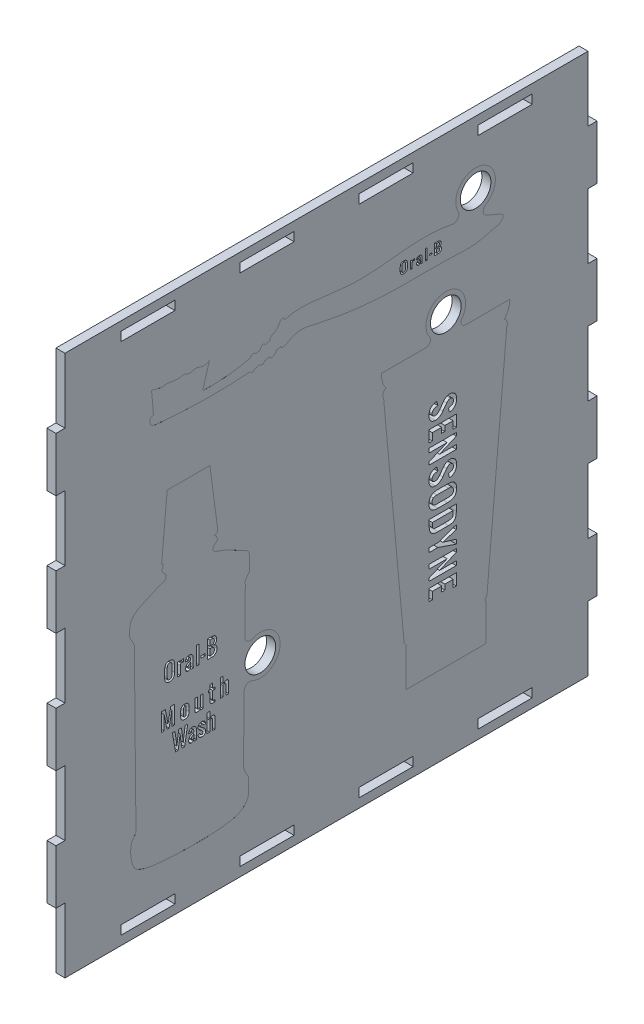
SolidWorks part; units mm, degrees
material "Maple"
ref_plane "Front Plane" through (0, 0, 0) normal (0, 0, 1) x (1, 0, 0)
ref_plane "Top Plane" through (0, 0, 0) normal (0, 1, 0) x (1, 0, 0)
ref_plane "Right Plane" through (0, 0, 0) normal (1, 0, 0) x (0, 0, -1)
sketch "Sketch1" plane through (0, 0, 0) normal (1, 0, 0) x (0, 0, -1)
  line L0 (-35.3846, 0) -> (34.2308, 0)
  line L1 (-145, -150) -> (145, -150)
  line L2 (-145, -150) -> (-145, 150) construction
  line L3 (-145, 150) -> (145, 150)
  line L4 (145, -150) -> (145, 150) construction
  line L5 (-145, -150) -> (145, 150) construction
  line L6 (-145, 150) -> (145, -150) construction
  line L7 (0, 33.2692) -> (0, -29.4231)
  line L8 (-150, 92.5) -> (-150, -92.5) construction
  line L9 (-145, 145) -> (145, 145) construction
  line L10 (-114, -140) -> (-84, -140)
  line L11 (-84, -145) -> (-84, -140)
  line L12 (-145, 150) -> (-145, 114)
  line L13 (-145, 114) -> (-150, 114)
  line L14 (-150, 114) -> (-150, 84)
  line L15 (-150, 84) -> (-145, 84)
  line L16 (150, 114) -> (150, 84)
  line L17 (150, 84) -> (145, 84)
  line L18 (145, 114) -> (150, 114)
  line L19 (145, 150) -> (145, 114)
  line L20 (-114, -145) -> (-84, -145)
  line L21 (-114, 145) -> (-84, 145)
  line L22 (-114, 145) -> (-114, 140)
  line L23 (-114, 140) -> (-84, 140)
  line L24 (-84, 145) -> (-84, 140)
  line L25 (-114, -145) -> (-114, -140)
  line L26 (-145, 84) -> (-145, 48)
  line L27 (-150, 48) -> (-150, 18)
  line L28 (-150, 18) -> (-145, 18)
  line L29 (145, 84) -> (145, 48)
  line L30 (145, 48) -> (150, 48)
  line L31 (150, 48) -> (150, 18)
  line L32 (150, 18) -> (145, 18)
  line L33 (-145, 48) -> (-150, 48)
  line L34 (-145, 18) -> (-145, -18)
  line L35 (-150, -18) -> (-150, -48)
  line L36 (-150, -48) -> (-145, -48)
  line L37 (145, 18) -> (145, -18)
  line L38 (145, -18) -> (150, -18)
  line L39 (150, -18) -> (150, -48)
  line L40 (150, -48) -> (145, -48)
  line L41 (-145, -18) -> (-150, -18)
  line L42 (-145, -48) -> (-145, -84)
  line L43 (-150, -84) -> (-150, -114)
  line L44 (-150, -114) -> (-145, -114)
  line L45 (145, -48) -> (145, -84)
  line L46 (145, -84) -> (150, -84)
  line L47 (150, -84) -> (150, -114)
  line L48 (150, -114) -> (145, -114)
  line L49 (-145, -84) -> (-150, -84)
  line L50 (-145, -114) -> (-145, -150)
  line L51 (145, -114) -> (145, -150)
  line L52 (-48, 145) -> (-48, 140)
  line L53 (-48, 145) -> (-18, 145)
  line L54 (-18, 145) -> (-18, 140)
  line L55 (-48, 140) -> (-18, 140)
  line L56 (-48, -140) -> (-18, -140)
  line L57 (-18, -145) -> (-18, -140)
  line L58 (-48, -145) -> (-18, -145)
  line L59 (-48, -145) -> (-48, -140)
  line L60 (18, 145) -> (18, 140)
  line L61 (18, 145) -> (48, 145)
  line L62 (48, 145) -> (48, 140)
  line L63 (18, 140) -> (48, 140)
  line L64 (18, -140) -> (48, -140)
  line L65 (48, -145) -> (48, -140)
  line L66 (18, -145) -> (48, -145)
  line L67 (18, -145) -> (18, -140)
  line L68 (84, 145) -> (84, 140)
  line L69 (84, 145) -> (114, 145)
  line L70 (114, 145) -> (114, 140)
  line L71 (84, 140) -> (114, 140)
  line L72 (84, -140) -> (114, -140)
  line L73 (114, -145) -> (114, -140)
  line L74 (84, -145) -> (114, -145)
  line L75 (84, -145) -> (84, -140)
  line L76 (-114, 142.5) -> (-150, 142.5)
  line L77 (-84, 142.5) -> (-48, 142.5)
  point P0 (0, 0)
  dimension "D1" = 30
  dimension "D2" = 5
  dimension "D4" = 300
  dimension "D5" = 300
  dimension "D7" = 5
  dimension "D3" = 4
  dimension "D6" = 4
extrude "Boss-Extrude1" add sketch "Sketch1" along normal mid plane 5 contours L21 L24 L52 L53 L54 L55 L23 L22 L12 L13 L14 L15 L26 L33 L27 L28 L34 L41 L35 L36 L42 L49 L43 L44 L50 L1 L51 L48 L47 L46 L45 L40 L39 L38 L37 L32 region at (0, -132, 140.7574)
sketch "Sketch2" plane through (2.5, 0, 0) normal (1, 0, 0) x (0, 0, -1)
  line L0 (-103.805, 83.6641) -> (84.0248, 85.8672) construction
  line L1 (-64.9288, 106.4569) -> (-68.6513, 93.7878)
  line L2 (-96.9816, 107.9556) -> (-95.8726, 95.5327)
  circle A0 centre (82.6585, 114.1691) radius 8.5
  circle A1 centre (82.6585, 114.1691) radius 11 construction
  arc A2 (72.9982, 108.9081) -> (69.8228, 104.5224) centre (70.3636, 107.4733) cw
  arc A3 (72.9982, 108.9081) -> (88.3141, 104.7343) centre (82.6585, 114.1691) cw
  arc A4 (88.3141, 104.7343) -> (88.7976, 99.3543) centre (89.8565, 102.1612) ccw
  spline S0 degree 3 poles (6.5525, 104.4755) (16.2684, 102.9345) (33.0134, 104.2463) (57.7385, 107.1926) (78.973, 102.9316) (90.9553, 98.7316) (98.7094, 95.0038) (96.4944, 91.4648) (91.7278, 90.9878) (83.0886, 87.9475) (64.662, 89.4058) (34.2571, 88.137) (5.7252, 91.4149) (-14.3848, 96.6768) (-20.3547, 94.2318) (-22.9189, 92.5456) (-25.3044, 92.1896) (-25.2927, 93.3515) knots 0 0 0 0 0.133177 0.227569 0.341196 0.412109 0.424808 0.435895 0.455974 0.488682 0.560107 0.702904 0.90474 0.954569 0.976853 0.98794 1 1 1 1
  spline S1 degree 1 poles (-25.2927, 93.3515) (-28.0596, 92.6972) knots 0 0 1 1
  spline S2 degree 3 poles (-28.0596, 92.6972) (-27.8287, 90.8983) (-31.6114, 89.672) (-31.7862, 91.8044) knots 0 0 0 0 1 1 1 1
  spline S3 degree 1 poles (-31.7862, 91.8044) (-34.374, 90.9522) knots 0 0 1 1
  spline S4 degree 2 poles (-34.374, 90.9522) (-35.327, 88.9008) (-37.169, 90.4587) knots 0 0 0 1 1 1
  spline S5 degree 1 poles (-37.169, 90.4587) (-39.7568, 89.818) knots 0 0 1 1
  spline S6 degree 2 poles (-39.7568, 89.818) (-41.1273, 88.159) (-42.5517, 89.818) knots 0 0 0 1 1 1
  spline S7 degree 3 poles (-42.5517, 89.818) (-55.7829, 88.5362) (-74.5574, 88.9284) (-91.126, 90.1625) (-97.6029, 90.8687) (-97.837, 93.4725) (-97.9211, 96.0213) (-96.2777, 95.4349) (-95.8726, 95.5327) knots 0 0 0 0 0.683272 0.847161 0.913324 0.939394 0.976423 1 1 1 1
  spline S8 degree 3 poles (-96.9816, 107.9556) (-95.1572, 108.0377) (-92.2331, 106.176) (-88.4707, 107.3482) (-85.9029, 106.6264) (-83.8994, 106.6299) (-81.5057, 106.1616) (-79.0534, 107.2928) (-76.9027, 105.7554) (-74.5329, 105.9127) (-72.0913, 106.8487) (-68.9379, 105.1119) (-66.2637, 105.4954) (-64.9288, 106.4569) knots 0 0 0 0 0.164786 0.287539 0.337088 0.406149 0.470446 0.558401 0.626387 0.691386 0.769448 0.854065 1 1 1 1
  spline S9 degree 2 poles (-68.6513, 93.7878) (-55.1915, 93.1744) (-42.0352, 96.4052) knots 0 0 0 1 1 1
  spline S10 degree 3 poles (-42.0352, 96.4052) (-41.9645, 97.6813) (-39.791, 98.0736) (-39.4213, 96.8815) knots 0 0 0 0 1 1 1 1
  spline S11 degree 1 poles (-36.6699, 97.363) (-39.4213, 96.8815) knots 0 0 1 1
  spline S12 degree 3 poles (-36.6699, 97.363) (-36.6714, 98.6626) (-34.5693, 100.4662) (-33.8498, 98.4635) knots 0 0 0 0 1 1 1 1
  spline S13 degree 1 poles (-33.8498, 98.4635) (-31.3721, 99.3578) knots 0 0 1 1
  spline S14 degree 3 poles (-31.3721, 99.3578) (-31.5133, 100.8043) (-29.3265, 101.6154) (-26.3053, 103.4262) (-25.9522, 106.0297) (-24.495, 106.4569) knots 0 0 0 0 0.331857 0.63536 1 1 1 1
  spline S15 degree 2 poles (-24.495, 106.4569) (-23.3753, 106.347) (-23.1115, 105.1401) knots 0 0 0 1 1 1
  spline S16 degree 3 poles (6.5525, 104.4755) (-3.0815, 105.0737) (-13.4853, 108.1798) (-23.1115, 105.1401) knots 0 0 0 0 1 1 1 1
  point P81 (0, 0)
  point P82 (0, 0)
  point P83 (84.1802, 119.7003)
  point P84 (84.1802, 119.7003)
  point P85 (0, 0)
extrude "Cut-Extrude1" cut sketch "Sketch2" against normal through all contours S0 S16 S15 S14 S13 S12 S11 S10 S9 L1 S8 L2 S7 S6 S5 S4 S3 S2 S1 | A2 S0 A4 A3 A0 | A0 region at (2.5, 97.1703, -2.8666) region at (2.5, 105.5078, -73.0782) region at (2.5, 114.1691, -82.6585)
sketch "Sketch3" plane through (2.5, 0, 0) normal (1, 0, 0) x (0, 0, -1)
  line L0 (-25.3812, -30.9825) -> (162.6317, -33) construction
  line L1 (31.6753, 39.8057) -> (43.0136, -82.9441)
  line L2 (44.0297, -85.902) -> (44.0297, -106.1138)
  line L3 (44.0297, -106.1138) -> (88.3586, -106.1138)
  line L4 (88.3586, -106.1138) -> (88.3586, -85.902)
  line L5 (88.9681, -82.9441) -> (99.9172, 39.8057)
  line L6 (101.6714, 52.5676) -> (30.6093, 52.5676)
  circle A0 centre (66.1403, 62.9692) radius 8.5
  circle A1 centre (66.1403, 62.9692) radius 11 construction
  arc A2 (57.2067, 56.5513) -> (55.1635, 52.5676) centre (55.1635, 55.0834) cw
  arc A3 (57.2067, 56.5513) -> (75.074, 56.5513) centre (66.1403, 62.9692) cw
  arc A4 (75.074, 56.5513) -> (77.1172, 52.5676) centre (77.1172, 55.0834) ccw
  spline S0 degree 2 poles (30.6093, 52.5676) (30.0746, 47.7888) (33.0459, 44.4632) knots 0 0 0 1 1 1
  spline S1 degree 2 poles (33.0459, 44.4632) (30.5043, 42.9078) (31.6753, 39.8057) knots 0 0 0 1 1 1
  spline S2 degree 2 poles (101.6714, 52.5676) (101.4143, 47.9068) (98.5767, 44.4632) knots 0 0 0 1 1 1
  spline S3 degree 2 poles (98.5767, 44.4632) (101.0752, 42.8843) (99.9172, 39.8057) knots 0 0 0 1 1 1
  spline S4 degree 2 poles (43.0136, -82.9441) (43.193, -84.2249) (44.4027, -84.7365) knots 0 0 0 1 1 1
  spline S5 degree 2 poles (44.4027, -84.7365) (43.7281, -85.1056) (44.0297, -85.902) knots 0 0 0 1 1 1
  spline S6 degree 2 poles (88.9681, -82.9441) (88.6722, -84.1285) (87.6529, -84.7365) knots 0 0 0 1 1 1
  spline S7 degree 2 poles (87.6529, -84.7365) (88.2852, -85.1047) (88.3586, -85.902) knots 0 0 0 1 1 1
  point P33 (0, 0)
  point P34 (66.1403, 52.5676)
  point P35 (0, 0)
  point P36 (0, 0)
  point P37 (0, 0)
  point P38 (0, 0)
  point P39 (0, 0)
  point P40 (80.7843, 50.0055)
  point P41 (81.0172, 51.8688)
  point P42 (66.1403, 62.9692)
  point P43 (55.1635, 52.5676)
  dimension "D1" = 11
  dimension "D2" = 17
extrude "Cut-Extrude4" cut sketch "Sketch3" against normal through all contours L1 L0 L5 S3 S2 L6 S0 S1 | A4 A3 A2 L6 A0 | A0 | S7 L4 L3 L2 S5 S4 L1 S1 S0 L6 S2 S3 L5 S6 region at (2.5, -20.1434, -65.9177) region at (2.5, 53.7952, -57.6751) region at (2.5, 62.9692, -66.1403)
sketch "Sketch4" plane through (2.5, 0, 0) normal (1, 0, 0) x (0, 0, -1)
  line L0 (56.9565, 29.9553) -> (56.9565, -75.6719) construction
  text T0 "SENSODYNE" font "Oswald" height 15
sketch "Sketch5" plane through (2.5, 0, 0) normal (1, 0, 0) x (0, 0, -1)
  line L0 (-164.1642, 33.9777) -> (0, 33.9777) construction
  line L1 (-64.6546, 55.9013) -> (-88.3352, 55.9013)
  line L2 (-88.3352, 55.9013) -> (-91.3122, 23.0192)
  line L3 (-64.6546, 55.9013) -> (-60.3245, 23.0192)
  line L4 (-106.526, -10.8034) -> (-105.639, -99.3563)
  line L5 (-45.0182, -10.8034) -> (-46.061, -98.1311)
  line L6 (-43.2783, -104.3785) -> (-43.2783, -112.242)
  circle A0 centre (-36.6998, -49.1357) radius 8.5
  circle A1 centre (-36.6998, -49.1357) radius 11 construction
  arc A2 (-41.1177, -39.0618) -> (-45.3224, -36.2786) centre (-42.3226, -36.3144) cw
  arc A3 (-41.1177, -39.0618) -> (-41.357, -59.1011) centre (-36.6998, -49.1357) cw
  arc A4 (-41.357, -59.1011) -> (-45.627, -61.7832) centre (-42.6272, -61.819) ccw
  spline S0 degree 3 poles (-46.061, -98.1311) (-45.5535, -100.3758) (-44.3748, -102.3812) (-43.2783, -104.3785) knots 0 0 0 0 1 1 1 1
  spline S1 degree 3 poles (-43.2783, -112.242) (-43.4166, -115.0045) (-46.5872, -118.7905) (-53.4587, -120.7059) (-62.491, -121.5767) (-74.8863, -121.9531) (-89.4824, -121.1309) (-100.1013, -120.2727) (-106.6348, -117.0775) (-108.4782, -111.9364) (-108.7832, -106.9022) (-107.8798, -102.1735) (-105.9409, -100.7903) (-105.639, -99.3563) knots 0 0 0 0 0.091092 0.156397 0.243947 0.407749 0.586765 0.756523 0.770177 0.837032 0.92551 0.950709 1 1 1 1
  spline S2 degree 2 poles (-91.3122, 23.0192) (-91.6801, 21.7652) (-90.3186, 21.1745) knots 0 0 0 1 1 1
  spline S3 degree 2 poles (-60.3245, 23.0192) (-60.2552, 21.1929) (-62.4896, 21.1745) knots 0 0 0 1 1 1
  spline S4 degree 3 poles (-62.4896, 21.1745) (-61.2991, 20.9908) (-59.3865, 17.7511) (-62.4979, 16.7748) (-63.1688, 15.0158) (-62.2048, 13.0592) (-58.0441, 12.0721) (-52.9127, 9.4872) (-47.7641, 6.5137) (-43.2354, 4.6448) (-42.275, 0.4691) (-42.9963, -2.6108) (-42.4325, -6.0325) (-44.4143, -7.916) (-45.4392, -9.558) (-45.0182, -10.8034) knots 0 0 0 0 0.086801 0.139575 0.170697 0.196999 0.27023 0.427059 0.575154 0.667009 0.715592 0.836361 0.876038 0.926558 1 1 1 1
  spline S5 degree 3 poles (-90.3186, 21.1745) (-91.011, 20.2151) (-91.7958, 17.3683) (-88.9651, 16.3382) (-88.9562, 14.8445) (-89.0422, 13.033) (-92.603, 12.2808) (-96.8466, 10.2172) (-102.747, 7.9178) (-108.5698, 4.3722) (-109.1107, -0.4843) (-109.8272, -5.3852) (-106.2449, -8.1823) (-106.526, -10.8034) knots 0 0 0 0 0.086306 0.139113 0.156983 0.18213 0.252943 0.352661 0.518218 0.680568 0.758803 0.835283 1 1 1 1
  point P59 (0, 0)
  dimension "D1" = 11
extrude "Cut-Extrude7" cut sketch "Sketch5" against normal through all contours S2 S5 L4 S1 L6 S0 L5 S4 S3 L3 L1 L2 | A4 A3 A2 L5 A0 | A0 region at (2.5, -43.2536, 75.8314) region at (2.5, -39.0859, 44.1572) region at (2.5, -49.1357, 36.6998)
sketch "Sketch6" plane through (2.5, 0, 0) normal (1, 0, 0) x (0, 0, -1)
  line L0 (-90.2637, -36.7166) -> (-62.9603, -36.7166) construction
  line L1 (-92.3146, -58.8925) -> (-54.5001, -58.8925) construction
  line L2 (-92.3146, -72.0955) -> (-54.5001, -72.0955) construction
  text T0 "Oral-B" font "Oswald" height 10
  text T1 "Mouth" font "Oswald" height 10
  text T2 "Wash" font "Oswald" height 10
  point P7 (-73.4074, -58.8925)
  point P8 (-73.4074, -72.0955)
sketch "Sketch7" plane through (2.5, 0, 0) normal (1, 0, 0) x (0, 0, -1)
  line L0 (31.3279, 94.3287) -> (73.1618, 94.3287) construction
  text T0 "Oral-B" font "Oswald" height 6
sketch "Sketch8" plane through (2.5, 0, 0) normal (1, 0, 0) x (0, 0, -1)
  line L0 (-43.2783, -112.242) -> (-43.2783, -104.3785) construction
  line L1 (-64.6546, 55.9013) -> (-88.3352, 55.9013) construction
  line L3 (-106.526, -10.8034) -> (-105.639, -99.3563) construction
  line L4 (-60.3245, 23.0192) -> (-64.6546, 55.9013) construction
  line L5 (-88.3352, 55.9013) -> (-91.3122, 23.0192) construction
  line L6 (-43.2783, -112.242) -> (-43.2783, -104.3785)
  line L7 (-64.6546, 55.9013) -> (-88.3352, 55.9013)
  line L9 (-106.526, -10.8034) -> (-105.639, -99.3563)
  line L10 (-60.3245, 23.0192) -> (-64.6546, 55.9013)
  line L11 (-88.3352, 55.9013) -> (-91.3122, 23.0192)
  line L12 (101.6714, 52.5676) -> (77.1172, 52.5676) construction
  line L13 (88.3586, -106.1138) -> (88.3586, -85.902) construction
  line L14 (44.0297, -85.902) -> (44.0297, -106.1138) construction
  line L15 (44.0297, -106.1138) -> (88.3586, -106.1138) construction
  line L16 (88.9681, -82.9441) -> (99.9172, 39.8057) construction
  line L18 (31.6753, 39.8057) -> (43.0136, -82.9441) construction
  line L19 (88.3586, -106.1138) -> (88.3586, -85.902)
  line L20 (44.0297, -85.902) -> (44.0297, -106.1138)
  line L21 (44.0297, -106.1138) -> (88.3586, -106.1138)
  line L22 (88.9681, -82.9441) -> (99.9172, 39.8057)
  line L24 (31.6753, 39.8057) -> (43.0136, -82.9441)
  line L30 (-68.6513, 93.7878) -> (-64.9288, 106.4569) construction
  line L31 (-96.9816, 107.9556) -> (-95.8726, 95.5327) construction
  line L32 (-33.8498, 98.4635) -> (-31.3721, 99.3578)
  line L33 (-39.4213, 96.8815) -> (-36.6699, 97.363)
  line L34 (-37.169, 90.4587) -> (-39.7568, 89.818)
  line L35 (-31.7862, 91.8044) -> (-34.374, 90.9522)
  line L36 (-25.2927, 93.3515) -> (-28.0596, 92.6972)
  line L37 (-68.6513, 93.7878) -> (-64.9288, 106.4569)
  line L38 (-96.9816, 107.9556) -> (-95.8726, 95.5327)
  line L39 (55.1635, 52.5676) -> (30.6093, 52.5676) construction
  line L40 (101.6714, 52.5676) -> (77.1172, 52.5676)
  line L41 (55.1635, 52.5676) -> (30.6093, 52.5676)
  line L42 (-45.0182, -10.8034) -> (-45.3224, -36.2786) construction
  line L43 (-45.627, -61.7832) -> (-46.061, -98.1311) construction
  line L44 (-45.0182, -10.8034) -> (-45.3224, -36.2786)
  line L45 (-45.627, -61.7832) -> (-46.061, -98.1311)
  arc A1 (88.3141, 104.7343) -> (88.7976, 99.3543) centre (89.8565, 102.1612) ccw construction
  arc A2 (88.3141, 104.7343) -> (72.9982, 108.9081) centre (82.6585, 114.1691) ccw construction
  arc A3 (69.8228, 104.5224) -> (72.9982, 108.9081) centre (70.3636, 107.4733) ccw construction
  circle A4 centre (82.6585, 114.1691) radius 8.5
  arc A5 (88.3141, 104.7343) -> (88.7976, 99.3543) centre (89.8565, 102.1612) ccw
  arc A6 (88.3141, 104.7343) -> (72.9982, 108.9081) centre (82.6585, 114.1691) ccw
  arc A7 (69.8228, 104.5224) -> (72.9982, 108.9081) centre (70.3636, 107.4733) ccw
  arc A8 (75.074, 56.5513) -> (77.1172, 52.5676) centre (77.1172, 55.0834) ccw construction
  arc A10 (55.1635, 52.5676) -> (57.2067, 56.5513) centre (55.1635, 55.0834) ccw construction
  arc A12 (75.074, 56.5513) -> (77.1172, 52.5676) centre (77.1172, 55.0834) ccw
  circle A13 centre (66.1403, 62.9692) radius 8.5
  arc A14 (55.1635, 52.5676) -> (57.2067, 56.5513) centre (55.1635, 55.0834) ccw
  arc A15 (75.074, 56.5513) -> (57.2067, 56.5513) centre (66.1403, 62.9692) ccw
  arc A16 (-41.357, -59.1011) -> (-45.627, -61.7832) centre (-42.6272, -61.819) ccw construction
  arc A18 (-41.357, -59.1011) -> (-41.1177, -39.0618) centre (-36.6998, -49.1357) ccw construction
  arc A19 (-45.3224, -36.2786) -> (-41.1177, -39.0618) centre (-42.3226, -36.3144) ccw construction
  arc A20 (-41.357, -59.1011) -> (-45.627, -61.7832) centre (-42.6272, -61.819) ccw
  circle A21 centre (-36.6998, -49.1357) radius 8.5
  arc A22 (-41.357, -59.1011) -> (-41.1177, -39.0618) centre (-36.6998, -49.1357) ccw
  arc A23 (-45.3224, -36.2786) -> (-41.1177, -39.0618) centre (-42.3226, -36.3144) ccw
  parabola Q0 (-62.4896, 21.1745) -> (-60.3245, 23.0192) focus (-61.1658, 22.2491) apex (-60.6439, 21.8394) construction
  parabola Q1 (-91.3122, 23.0192) -> (-90.3186, 21.1745) focus (-90.7661, 22.2763) apex (-91.3104, 22.0676) construction
  parabola Q2 (-62.4896, 21.1745) -> (-60.3245, 23.0192) focus (-61.1658, 22.2491) apex (-60.6439, 21.8394)
  parabola Q3 (-91.3122, 23.0192) -> (-90.3186, 21.1745) focus (-90.7661, 22.2763) apex (-91.3104, 22.0676)
  parabola Q4 (87.6529, -84.7365) -> (88.3586, -85.902) focus (87.5479, -85.4891) apex (88.0641, -85.0928) construction
  parabola Q5 (88.9681, -82.9441) -> (87.6529, -84.7365) focus (87.3836, -83.2377) apex (88.4267, -84.069) construction
  parabola Q6 (44.4027, -84.7365) -> (44.0297, -85.902) focus (44.3159, -85.2845) apex (43.9975, -85.1451) construction
  parabola Q7 (43.0136, -82.9441) -> (44.4027, -84.7365) focus (44.2296, -83.4059) apex (43.4286, -84.0038) construction
  parabola Q8 (87.6529, -84.7365) -> (88.3586, -85.902) focus (87.5479, -85.4891) apex (88.0641, -85.0928)
  parabola Q9 (88.9681, -82.9441) -> (87.6529, -84.7365) focus (87.3836, -83.2377) apex (88.4267, -84.069)
  parabola Q10 (44.4027, -84.7365) -> (44.0297, -85.902) focus (44.3159, -85.2845) apex (43.9975, -85.1451)
  parabola Q11 (43.0136, -82.9441) -> (44.4027, -84.7365) focus (44.2296, -83.4059) apex (43.4286, -84.0038)
  parabola Q12 (33.0459, 44.4632) -> (31.6753, 39.8057) focus (32.8746, 42.2623) apex (31.538, 42.8192) construction
  parabola Q14 (98.5767, 44.4632) -> (99.9172, 39.8057) focus (98.6969, 42.2561) apex (100.0554, 42.8133) construction
  parabola Q15 (101.6714, 52.5676) -> (98.5767, 44.4632) focus (94.448, 50.0889) apex (100.3776, 47.2918) construction
  parabola Q16 (33.0459, 44.4632) -> (31.6753, 39.8057) focus (32.8746, 42.2623) apex (31.538, 42.8192)
  parabola Q18 (98.5767, 44.4632) -> (99.9172, 39.8057) focus (98.6969, 42.2561) apex (100.0554, 42.8133)
  parabola Q19 (101.6714, 52.5676) -> (98.5767, 44.4632) focus (94.448, 50.0889) apex (100.3776, 47.2918)
  parabola Q22 (-23.1115, 105.1401) -> (-24.495, 106.4569) focus (-24.0856, 105.6445) apex (-23.6862, 106.1563) construction
  parabola Q23 (-42.0352, 96.4052) -> (-68.6513, 93.7878) focus (-60.6914, 140.1901) apex (-57.0417, 93.9781) construction
  parabola Q24 (-42.5517, 89.818) -> (-39.7568, 89.818) focus (-41.1312, 89.577) apex (-41.1217, 88.9887)
  parabola Q25 (-37.169, 90.4587) -> (-34.374, 90.9522) focus (-35.6076, 90.3417) apex (-35.4786, 89.818)
  parabola Q26 (-23.1115, 105.1401) -> (-24.495, 106.4569) focus (-24.0856, 105.6445) apex (-23.6862, 106.1563)
  parabola Q27 (-42.0352, 96.4052) -> (-68.6513, 93.7878) focus (-60.6914, 140.1901) apex (-57.0417, 93.9781)
  parabola Q28 (30.6093, 52.5676) -> (33.0459, 44.4632) focus (35.5827, 49.0483) apex (31.269, 47.2602)
  spline S0 degree 3 poles (-2742.5498, 1330.6542) (5.6091, -122.6957) (-104.8352, -86.237) (-108.7832, -106.9022) (-108.4782, -111.9364) (-106.6348, -117.0775) (-100.1013, -120.2727) (-89.4824, -121.1309) (-74.8863, -121.9531) (-62.491, -121.5767) (-53.4587, -120.7059) (-15.6966, -110.1803) (-59.6585, 63.8728) (-3031.5563, -311.9062) knots -0.549236 -0.549236 -0.549236 -0.549236 0.049291 0.07449 0.162968 0.229823 0.243477 0.413235 0.592251 0.756053 0.843603 0.908908 2.096664 2.096664 2.096664 2.096664 only from (-105.639, -99.3563) to (-43.2783, -112.242) construction
  spline S1 degree 3 poles (-2885.8008, -1060.6798) (2862.4928, 742.5463) (-2944.3638, -964.9011) (2782.6842, 897.2561) knots -15.55403 -15.55403 -15.55403 -15.55403 15.743313 15.743313 15.743313 15.743313 only from (-43.2783, -104.3785) to (-46.061, -98.1311) construction
  spline S2 degree 3 poles (-1575.2983, -2584.2378) (85.9785, 158.0196) (-109.5975, 23.8459) (-88.9651, 16.3382) (-88.9562, 14.8445) (-89.0422, 13.033) (-92.603, 12.2808) (-96.8466, 10.2172) (-102.747, 7.9178) (-108.5698, 4.3722) (-109.1107, -0.4843) (-112.7776, -25.5685) (55.4837, -11.8156) (-3004.0815, -786.4549) knots -0.987214 -0.987214 -0.987214 -0.987214 0.086306 0.139113 0.156983 0.18213 0.252943 0.352661 0.518218 0.680568 0.758803 0.835283 2.315501 2.315501 2.315501 2.315501 only from (-90.3186, 21.1745) to (-106.526, -10.8034) construction
  spline S4 degree 3 poles (-43.2783, -104.3785) (-44.3748, -102.3812) (-45.5535, -100.3758) (-46.061, -98.1311) knots 0 0 0 0 1 1 1 1
  spline S5 degree 3 poles (-105.639, -99.3563) (-105.9409, -100.7903) (-107.8798, -102.1735) (-108.7832, -106.9022) (-108.4782, -111.9364) (-106.6348, -117.0775) (-100.1013, -120.2727) (-89.4824, -121.1309) (-74.8863, -121.9531) (-62.491, -121.5767) (-53.4587, -120.7059) (-46.5872, -118.7905) (-43.4166, -115.0045) (-43.2783, -112.242) knots 0 0 0 0 0.049291 0.07449 0.162968 0.229823 0.243477 0.413235 0.592251 0.756053 0.843603 0.908908 1 1 1 1
  spline S6 degree 3 poles (-90.3186, 21.1745) (-91.011, 20.2151) (-91.7958, 17.3683) (-88.9651, 16.3382) (-88.9562, 14.8445) (-89.0422, 13.033) (-92.603, 12.2808) (-96.8466, 10.2172) (-102.747, 7.9178) (-108.5698, 4.3722) (-109.1107, -0.4843) (-109.8272, -5.3852) (-106.2449, -8.1823) (-106.526, -10.8034) knots 0 0 0 0 0.086306 0.139113 0.156983 0.18213 0.252943 0.352661 0.518218 0.680568 0.758803 0.835283 1 1 1 1
  spline S7 degree 3 poles (-45.0182, -10.8034) (-45.4392, -9.558) (-44.4143, -7.916) (-42.4325, -6.0325) (-42.9963, -2.6108) (-42.275, 0.4691) (-43.2354, 4.6448) (-47.7641, 6.5137) (-52.9127, 9.4872) (-58.0441, 12.0721) (-62.2048, 13.0592) (-63.1688, 15.0158) (-62.4979, 16.7748) (-59.3865, 17.7511) (-61.2991, 20.9908) (-62.4896, 21.1745) knots 0 0 0 0 0.073442 0.123962 0.163639 0.284408 0.332991 0.424846 0.572941 0.72977 0.803001 0.829303 0.860425 0.913199 1 1 1 1
  spline S14 degree 3 poles (-1831.8486, 2540.3951) (-20.7773, 9.9839) (-98.2602, 106.2938) (-97.837, 93.4725) (-97.6029, 90.8687) (-91.126, 90.1625) (32.9365, 80.9219) (373.4952, 119.8653) (-2821.2546, 1206.7555) knots -0.349331 -0.349331 -0.349331 -0.349331 0.023577 0.060606 0.086676 0.152839 0.316728 6.925471 6.925471 6.925471 6.925471 only from (-95.8726, 95.5327) to (-42.5517, 89.818) construction
  spline S15 degree 3 poles (-2902.3044, 1054.9753) (31.6857, 319.1533) (-42.9103, 90.7771) (-72.0913, 106.8487) (-74.5329, 105.9127) (-76.9027, 105.7554) (-79.0534, 107.2928) (-81.5057, 106.1616) (-83.8994, 106.6299) (-85.9029, 106.6264) (-88.4707, 107.3482) (-111.9493, 100.0337) (-120.3168, 238.9042) (-505.4382, -2863.6554) knots -2.547225 -2.547225 -2.547225 -2.547225 0.145935 0.230552 0.308614 0.373613 0.441599 0.529554 0.593851 0.662912 0.712461 0.835214 2.76644 2.76644 2.76644 2.76644 only from (-64.9288, 106.4569) to (-96.9816, 107.9556) construction
  spline S16 degree 3 poles (-33.8498, 98.4635) (-34.5693, 100.4662) (-36.6714, 98.6626) (-36.6699, 97.363) knots 0 0 0 0 1 1 1 1
  spline S17 degree 3 poles (-39.4213, 96.8815) (-39.791, 98.0736) (-41.9645, 97.6813) (-42.0352, 96.4052) knots 0 0 0 0 1 1 1 1
  spline S18 degree 3 poles (-31.7862, 91.8044) (-31.6114, 89.672) (-27.8287, 90.8983) (-28.0596, 92.6972) knots 0 0 0 0 1 1 1 1
  spline S19 degree 3 poles (-24.495, 106.4569) (-25.9522, 106.0297) (-26.3053, 103.4262) (-29.3265, 101.6154) (-31.5133, 100.8043) (-31.3721, 99.3578) knots 0 0 0 0 0.36464 0.668143 1 1 1 1
  spline S20 degree 3 poles (6.5525, 104.4755) (-3.0815, 105.0737) (-13.4853, 108.1798) (-23.1115, 105.1401) knots 0 0 0 0 1 1 1 1
  spline S21 degree 3 poles (-2620.0063, 1387.0751) (149.1048, -2.32) (25.8344, 130.0388) (98.7094, 95.0038) (96.4944, 91.4648) (91.7278, 90.9878) (83.0886, 87.9475) (64.662, 89.4058) (34.2571, 88.137) (5.7252, 91.4149) (-14.3848, 96.6768) (-20.3547, 94.2318) (-30.1514, 87.7896) (-84.7849, 103.6645) (2256.2114, 2039.2052) knots -0.45411 -0.45411 -0.45411 -0.45411 0.412109 0.424808 0.435895 0.455974 0.488682 0.560107 0.702904 0.90474 0.954569 0.976853 0.98794 1.128142 1.128142 1.128142 1.128142 only from (88.7976, 99.3543) to (-25.2927, 93.3515) construction
  spline S22 degree 3 poles (-95.8726, 95.5327) (-96.2777, 95.4349) (-97.9211, 96.0213) (-97.837, 93.4725) (-97.6029, 90.8687) (-91.126, 90.1625) (-74.5574, 88.9284) (-55.7829, 88.5362) (-42.5517, 89.818) knots 0 0 0 0 0.023577 0.060606 0.086676 0.152839 0.316728 1 1 1 1
  spline S23 degree 3 poles (-64.9288, 106.4569) (-66.2637, 105.4954) (-68.9379, 105.1119) (-72.0913, 106.8487) (-74.5329, 105.9127) (-76.9027, 105.7554) (-79.0534, 107.2928) (-81.5057, 106.1616) (-83.8994, 106.6299) (-85.9029, 106.6264) (-88.4707, 107.3482) (-92.2331, 106.176) (-95.1572, 108.0377) (-96.9816, 107.9556) knots 0 0 0 0 0.145935 0.230552 0.308614 0.373613 0.441599 0.529554 0.593851 0.662912 0.712461 0.835214 1 1 1 1
  spline S24 degree 3 poles (-83.4805, 3094.8941) (-192.9576, 110.5912) (-65.5481, 92.5016) (157.6497, 119.0982) (316.9592, -156.6111) (-2446.522, 1736.4761) knots -1.360105 -1.360105 -1.360105 -1.360105 0.133177 0.227569 1.719926 1.719926 1.719926 1.719926 only from (6.5525, 104.4755) to (69.8228, 104.5224) construction
  spline S25 degree 3 poles (88.7976, 99.3543) (90.963, 98.5375) (94.1279, 97.2064) (98.7094, 95.0038) (96.4944, 91.4648) (91.7278, 90.9878) (83.0886, 87.9475) (64.662, 89.4058) (34.2571, 88.137) (5.7252, 91.4149) (-14.3848, 96.6768) (-20.3547, 94.2318) (-22.9189, 92.5456) (-25.3044, 92.1896) (-25.2927, 93.3515) knots 0.379942 0.379942 0.379942 0.379942 0.412109 0.424808 0.435895 0.455974 0.488682 0.560107 0.702904 0.90474 0.954569 0.976853 0.98794 1 1 1 1
  spline S26 degree 3 poles (6.5525, 104.4755) (16.2684, 102.9345) (33.0134, 104.2463) (53.8458, 106.7287) (65.4465, 105.3244) (69.8228, 104.5224) knots 0 0 0 0 0.133177 0.227569 0.287478 0.287478 0.287478 0.287478
extrude "Boss-Extrude2" add sketch "Sketch8" against normal through all separate body contours L44 S7 Q2 L10 L7 L11 Q3 S6 L9 S5 L6 S4 L45 A20 A22 A23 A21 | L41 Q28 Q16 L24 Q11 Q10 L20 L21 L19 Q8 Q9 L22 Q18 Q19 L40 A12 A15 A14 A13 | S26 S20 Q26 S19 L32 S16 L33 S17 Q27 L37 S23 L38 S22 Q24 L34 Q25 L35 S18 L36 S25 A5 A6 A7 A4 region at (2.5, -43.345, 75.2144) region at (2.5, -18.6346, -65.9218) region at (2.5, 98.2433, -8.5242)
extrude "Cut-Extrude8" cut sketch "Sketch7" against normal blind 2.5
extrude "Cut-Extrude9" cut sketch "Sketch6" against normal through all
extrude "Cut-Extrude10" cut sketch "Sketch4" against normal through all
